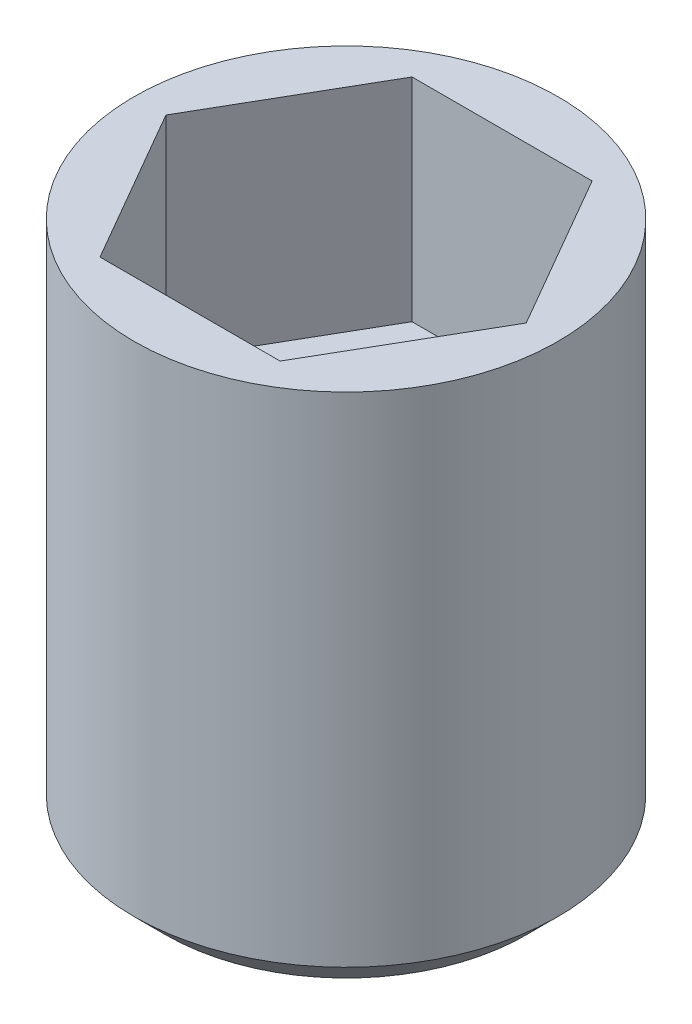
SolidWorks part; units mm, degrees
ref_plane "Alzado" through (0, 0, 0) normal (0, 0, 1) x (1, 0, 0)
ref_plane "Planta" through (0, 0, 0) normal (0, 1, 0) x (1, 0, 0)
ref_plane "Vista lateral" through (0, 0, 0) normal (1, 0, 0) x (0, 0, -1)
sketch "Croquis1" plane through (0, 0, 0) normal (0, 1, 0) x (1, 0, 0)
  circle A0 centre (0, 0) radius 2
  dimension "D1" = 4
extrude "Saliente-Extruir1" add sketch "Croquis1" along normal blind 5
cosmetic thread "Rosca cosmética1" parameters "D2"=3
sketch "Croquis2" plane through (0, 5, 0) normal (0, 1, 0) x (1, 0, 0)
  line L1 (1.6995, 0) -> (0.8498, 1.4718)
  line L2 (0.8498, 1.4718) -> (-0.8498, 1.4718)
  line L3 (-0.8498, 1.4718) -> (-1.6995, 0)
  line L4 (-1.6995, 0) -> (-0.8498, -1.4718)
  line L5 (-0.8498, -1.4718) -> (0.8498, -1.4718)
  line L6 (0.8498, -1.4718) -> (1.6995, 0)
  circle A0 centre (0, 0) radius 1.4718 construction
  point P0 (0, 0)
  dimension "D1" = 1.6995
extrude "Cortar-Extruir1" cut sketch "Croquis2" against normal blind 2
chamfer "Chaflán1" distance 0.3 angle 45 1 edges at (0, 0, 2)
